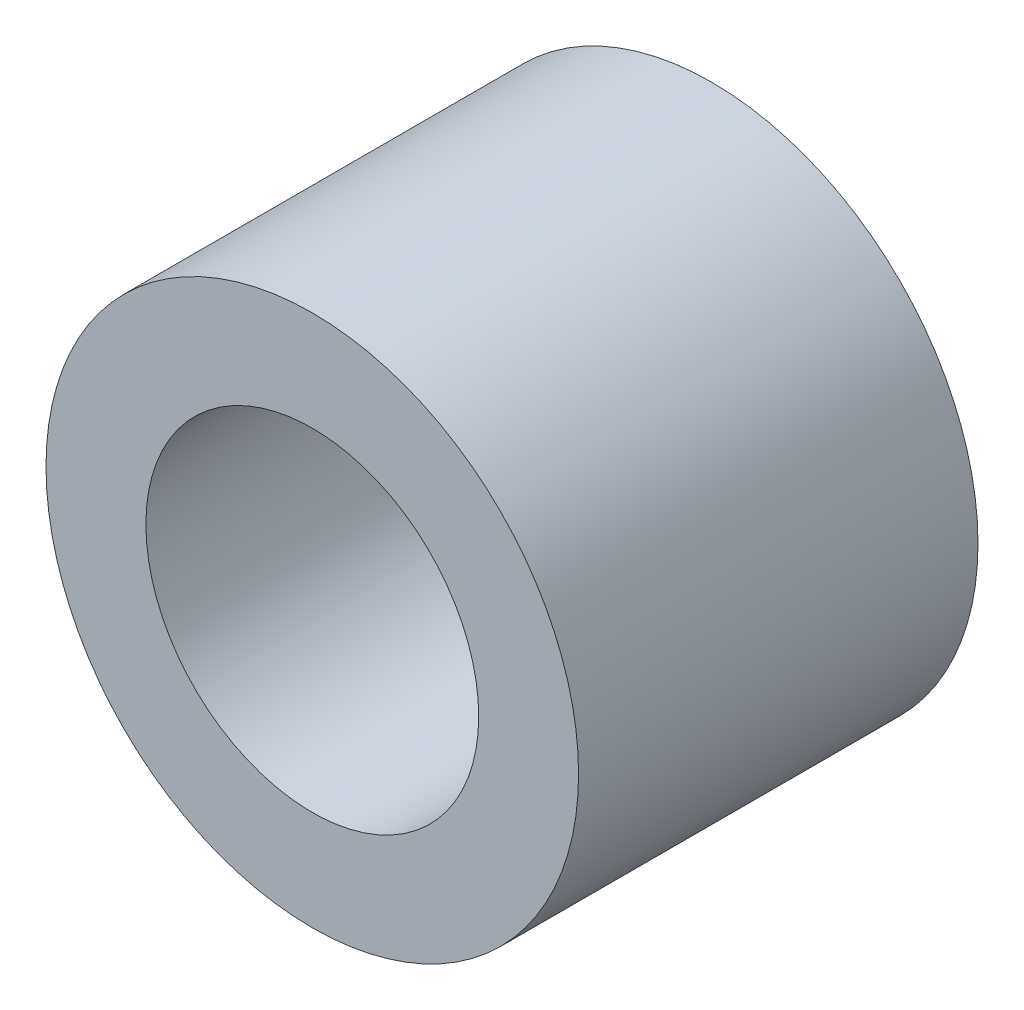
SolidWorks part; units mm, degrees
material "Tin Bearing Bronze"
ref_plane "Front Plane" through (0, 0, 0) normal (0, 0, 1) x (1, 0, 0)
ref_plane "Top Plane" through (0, 0, 0) normal (0, 1, 0) x (1, 0, 0)
ref_plane "Right Plane" through (0, 0, 0) normal (1, 0, 0) x (0, 0, -1)
sketch "Sketch1" plane through (0, 0, 0) normal (0, 0, 1) x (1, 0, 0)
  circle A0 centre (0, 0) radius 3.9688
  circle A1 centre (0, 0) radius 6.35
  dimension "D1" = 7.9375
  dimension "D2" = 12.7
extrude "Boss-Extrude1" add sketch "Sketch1" along normal blind 9.525
equation "\"dovetail-angle\" = 60"
equation "\"dovetail-stock-width\" = 5"
equation "\"dovetail-stock-height\" = 1.25"
equation "\"dovetail-depth\" = 0.5 * \"dovetail-stock-height\""
equation "\"dovetail-throat-width\" = \"dovetail-stock-width\" - (2 * \"dovetail-depth\")"
equation "\"delta-x\" = 6"
equation "\"delta-y\" = 3"
equation "\"delta-z\"= 2.5"
equation "\"gib-thickness\" = 0.25"
equation "\"x-slide-length\" = \"dovetail-stock-width\" + \"delta-x\""
equation "\"y-slide-length\" = \"dovetail-stock-width\" + \"delta-y\""
equation "\"dog-point-diam\" = .149"
equation "\"dog-point-length\" = .067"
equation "\"dovetail-double-height\" = 2 * \"dovetail-depth\" + 0.5"
equation "\"acme-major-diam\" = .5"
equation "\"acme-pitch-diam\" = 0.45"
equation "\"acme-minor-diam\" = 0.4"
equation "\"x-screw-length\" = \"x-slide-length\" + \"screw-add-length\""
equation "\"y-screw-length\" = \"y-slide-length\" + \"screw-add-length\""
equation "\"acme-nut-od\" = 1.47"
equation "\"acme-nut-length\" = 1"
equation "\"acme-nut-trim-height\" = .75"
equation "\"screw-bearing-od\" = 0.5"
equation "\"screw-bearing-length\" = .375"
equation "\"end-plate-thickness\" = \"screw-bearing-length\""
equation "\"screw-bearing-id\" = .3125"
equation "\"D1@Sketch1\"=\"screw-bearing-id\""
equation "\"D2@Sketch1\"=\"screw-bearing-od\""
equation "\"D1@Boss-Extrude1\"=\"screw-bearing-length\""
